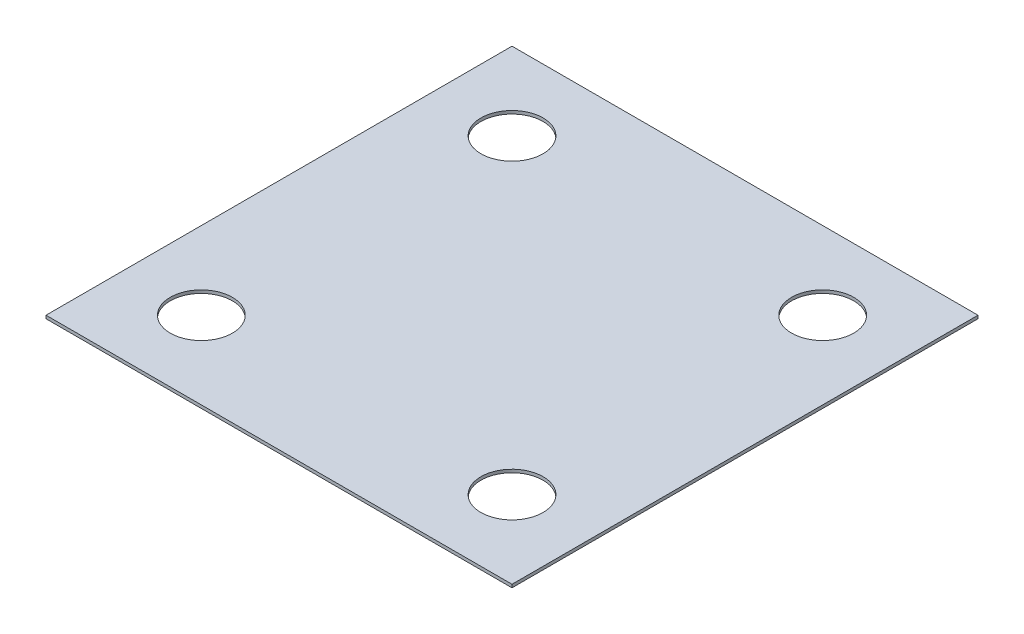
SolidWorks part; units mm, degrees
material "AISI 304"
ref_plane "前视基准面" through (0, 0, 0) normal (0, 0, 1) x (1, 0, 0)
ref_plane "上视基准面" through (0, 0, 0) normal (0, 1, 0) x (1, 0, 0)
ref_plane "右视基准面" through (0, 0, 0) normal (1, 0, 0) x (0, 0, -1)
sketch "Sketch1" plane through (0, 0, 0) normal (0, 1, 0) x (1, 0, 0)
  line L1 (-150, -150) -> (150, -150)
  line L2 (-150, -150) -> (-150, 150)
  line L3 (-150, 150) -> (150, 150)
  line L4 (150, -150) -> (150, 150)
  line L5 (-150, -150) -> (150, 150) construction
  line L6 (-150, 150) -> (150, -150) construction
  point P0 (0, 0)
  dimension "D1" = 300
  dimension "D2" = 300
base flange "Base-Flange1" sketch "Sketch1" thickness 2 reverse thickness direction no parameters "D1"=0.7366
sketch "Sketch6" plane through (0, 0, 0) normal (0, 1, 0) x (1, 0, 0)
  line L0 (-1.1, 0) -> (1.1, 0) construction
  line L1 (0, -1.1) -> (0, 1.1) construction
  circle A0 centre (100, 100) radius 20
  circle A1 centre (100, -100) radius 20
  circle A2 centre (-100, -100) radius 20
  circle A3 centre (-100, 100) radius 20
  point P14 (100, 100)
  point P15 (100, -100)
  point P16 (-100, -100)
  point P17 (-100, 100)
  dimension "D1" = 40
  dimension "D2" = 100
  dimension "D3" = 100
extrude "Cut-Extrude1" cut sketch "Sketch6" against normal through all normal cut yes
sketch "Bend-Lines1" plane through (0, 0, 0) normal (0, 1, 0) x (1, 0, 0)
sketch "Bounding-Box1" plane through (0, 0, 0) normal (0, 1, 0) x (1, 0, 0)
sheet metal parameters "Sheet-Metal6" thickness 2 parameters "D1"=0.7366
flat pattern "Flat-Pattern6" [suppressed]
sketch "Bend-Lines2" plane through (0, 0, 0) normal (0, 1, 0) x (1, 0, 0)
sketch "Bounding-Box2" [suppressed] plane through (0, 0, 0) normal (0, 1, 0) x (1, 0, 0)
sheet metal parameters "Sheet-Metal7" thickness 2 parameters "D1"=0.7366
flat pattern "Flat-Pattern7"
sketch "Bend-Lines3" plane through (0, 0, 0) normal (0, 1, 0) x (1, 0, 0)
sketch "Bounding-Box3" [suppressed] plane through (0, 0, 0) normal (0, 1, 0) x (1, 0, 0)
sheet metal parameters "Sheet-Metal8" thickness 2 parameters "D1"=0.7366
flat pattern "Flat-Pattern8"
sketch "Bend-Lines4" plane through (0, 0, 0) normal (0, 1, 0) x (1, 0, 0)
sketch "Bounding-Box4" [suppressed] plane through (0, 0, 0) normal (0, 1, 0) x (1, 0, 0)
sheet metal parameters "Sheet-Metal9" thickness 2 parameters "D1"=0.7366
flat pattern "Flat-Pattern9"
sketch "Bend-Lines5" plane through (0, 0, 0) normal (0, 1, 0) x (1, 0, 0)
sketch "Bounding-Box5" [suppressed] plane through (0, 0, 0) normal (0, 1, 0) x (1, 0, 0)
sheet metal parameters "Sheet-Metal10" thickness 2 parameters "D1"=0.7366
flat pattern "Flat-Pattern10"
sketch "Bend-Lines6" plane through (0, 0, 0) normal (0, 1, 0) x (1, 0, 0)
sketch "Bounding-Box6" [suppressed] plane through (0, 0, 0) normal (0, 1, 0) x (1, 0, 0)
sheet metal parameters "Sheet-Metal11" thickness 2 parameters "D1"=0.7366
flat pattern "Flat-Pattern6"
sketch "Bend-Lines2" plane through (0, 0, 0) normal (0, 1, 0) x (1, 0, 0)
sketch "Bounding-Box2" [suppressed] plane through (0, 0, 0) normal (0, 1, 0) x (1, 0, 0)
